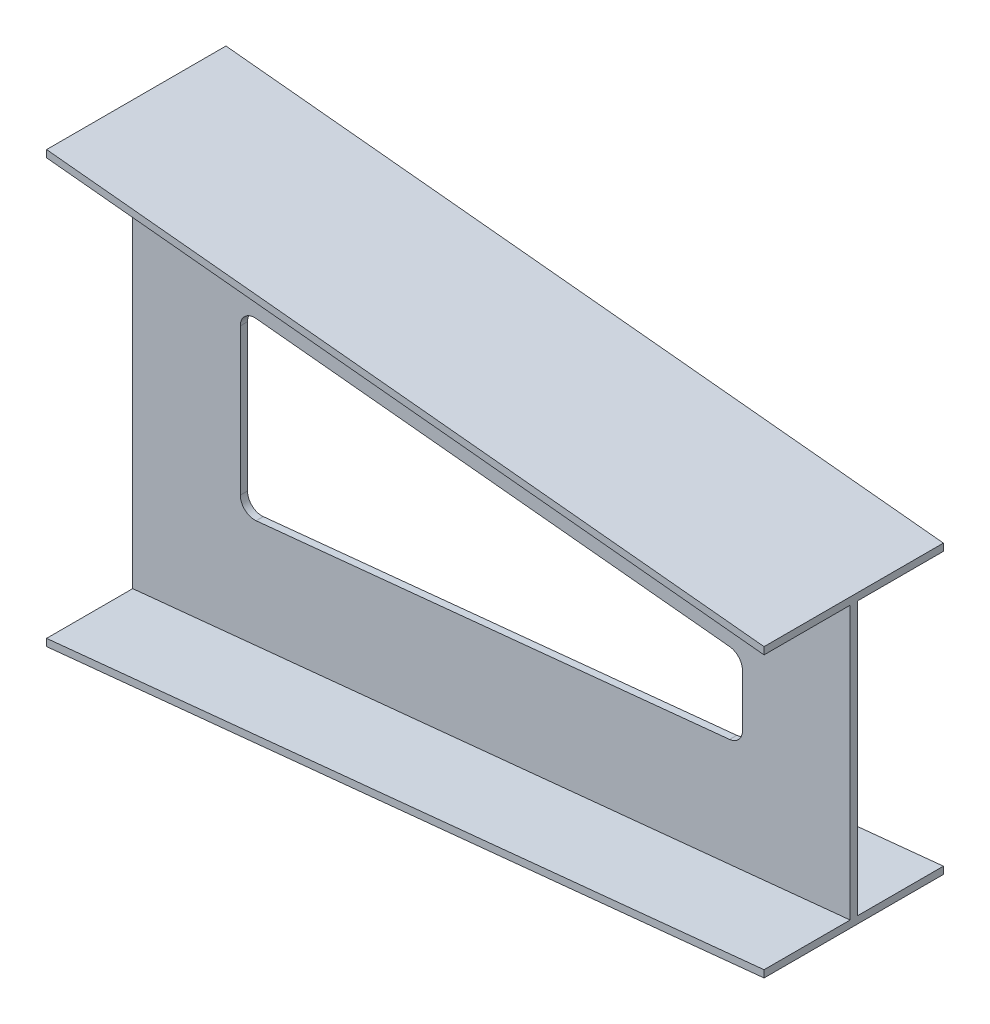
SolidWorks part; units mm, degrees
ref_plane "Front Plane" through (0, 0, 0) normal (0, 0, 1) x (1, 0, 0)
ref_plane "Top Plane" through (0, 0, 0) normal (0, 1, 0) x (1, 0, 0)
ref_plane "Right Plane" through (0, 0, 0) normal (1, 0, 0) x (0, 0, -1)
sketch "Sketch1" plane through (0, 0, 0) normal (1, 0, 0) x (0, 0, -1)
  line L1 (-130, 300) -> (120, 300)
  line L2 (-130, 300) -> (-130, 290)
  line L4 (120, 300) -> (120, 290)
  line L6 (-130, -290) -> (-130, -300)
  line L7 (-130, -300) -> (120, -300)
  line L8 (120, -290) -> (120, -300)
  line L15 (-130, -290) -> (-10, -290)
  line L16 (-5, 290) -> (-5, -690) construction
  line L18 (-130, 290) -> (-10, 290)
  line L19 (0, 0) -> (192.2403, 0) construction
  line L21 (-10, 290) -> (-10, -290)
  line L23 (0, 290) -> (0, -290)
  line L27 (0, 290) -> (120, 290)
  line L28 (0, -290) -> (120, -290)
  dimension "D1" = 250
  dimension "D2" = 10
  dimension "D3" = 600
  dimension "D4" = 10
ref_plane "Plane2" through (1000, 0, 0) normal (1, 0, 0) x (0, 0, -1)
sketch "Sketch4" plane through (1000, 0, -1000) normal (-1, 0, 0) x (0, 0, 1)
  line L1 (880, 200) -> (1130, 200)
  line L2 (880, 200) -> (880, 190)
  line L4 (1130, 200) -> (1130, 190)
  line L6 (880, -190) -> (880, -200)
  line L7 (880, -200) -> (1130, -200)
  line L8 (1130, -190) -> (1130, -200)
  line L15 (880, -190) -> (1000, -190)
  line L16 (1005, 390) -> (1005, -390) construction
  line L18 (880, 190) -> (1000, 190)
  line L19 (1010, -190) -> (1130, -190)
  line L21 (1000, 190) -> (1000, -190)
  line L23 (1010, 190) -> (1010, -190)
  line L24 (1010, 190) -> (1130, 190)
  line L26 (1010, 290) -> (1010, -290) construction
  line L27 (1000, 0) -> (820.2065, 0) construction
  dimension "D1" = 250
  dimension "D2" = 10
  dimension "D3" = 400
  dimension "D4" = 10
loft "Loft4" add profiles "Sketch1", "Sketch4" connector at (0, 290, 10) connector at (1000, 190, 10)
sketch "Sketch6" plane through (0, 0, 10) normal (0, 0, 1) x (1, 0, 0)
  line L8 (150, -124.2519) -> (850, -54.2519)
  line L9 (850, -54.2519) -> (850, 54.2519)
  line L10 (850, 54.2519) -> (150, 124.2519)
  line L11 (150, 124.2519) -> (150, -124.2519)
  line L12 (171.9901, -122.0529) -> (831.9901, -56.0529)
  line L13 (850, -36.1521) -> (850, 36.1521)
  line L14 (831.9901, 56.0529) -> (171.9901, 122.0529)
  line L15 (150, 102.1521) -> (150, -102.1521)
  arc A0 (150, -102.1521) -> (171.9901, -122.0529) centre (170, -102.1521) ccw
  arc A1 (850, 36.1521) -> (831.9901, 56.0529) centre (830, 36.1521) ccw
  arc A2 (850, -36.1521) -> (831.9901, -56.0529) centre (830, -36.1521) cw
  arc A3 (150, 102.1521) -> (171.9901, 122.0529) centre (170, 102.1521) cw
  dimension "D2" = 20
  dimension "D1" = 150
extrude "Cut-Extrude1" cut sketch "Sketch6" against normal blind 10
